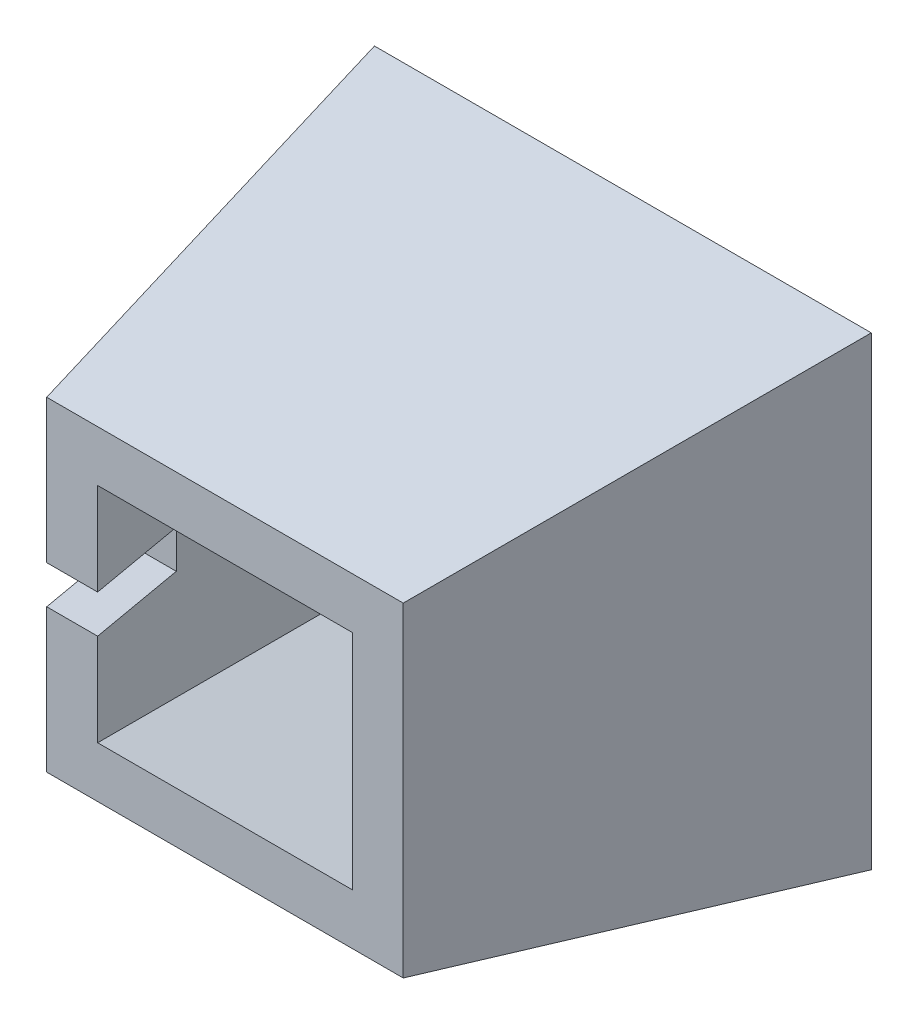
SolidWorks part; units mm, degrees
ref_plane "Front Plane" through (0, 0, 0) normal (0, 0, 1) x (1, 0, 0)
ref_plane "Top Plane" through (0, 0, 0) normal (0, 1, 0) x (1, 0, 0)
ref_plane "Right Plane" through (0, 0, 0) normal (1, 0, 0) x (0, 0, -1)
sketch "Sketch2" plane through (0, 0, 0) normal (0, 0, 1) x (1, 0, 0)
  line L1 (-56, -51) -> (56, -51)
  line L2 (-56, -51) -> (-56, 51)
  line L3 (-56, 51) -> (56, 51)
  line L4 (56, -51) -> (56, 51)
  line L5 (-56, -51) -> (56, 51) construction
  line L6 (-56, 51) -> (56, -51) construction
  point P0 (0, 0)
  dimension "D1" = 112
  dimension "D2" = 102
extrude "Boss-Extrude1" add sketch "Sketch2" against normal blind 125 draft 10 draft outward yes
sketch "Sketch3" plane through (0, 0, 0) normal (0, 0, -1) x (-1, 0, 0)
  line L1 (-40, -35) -> (40, -35)
  line L2 (-40, -35) -> (-40, 35)
  line L3 (-40, 35) -> (40, 35)
  line L4 (40, -35) -> (40, 35)
  line L5 (-40, -35) -> (40, 35) construction
  line L6 (-40, 35) -> (40, -35) construction
  point P0 (0, 0)
  dimension "D1" = 80
  dimension "D2" = 70
extrude "Cut-Extrude1" cut sketch "Sketch3" along normal up to next (125 mm away) draft 10 draft outward yes
ref_plane "Plane1" through (-60, 0, 0) normal (1, 0, 0) x (0, 0, -1)
sketch "Sketch5" plane through (-60, 0, 0) normal (1, 0, 0) x (0, 0, -1)
  line L0 (0, 51) -> (0, -51) construction
  line L1 (0, -6) -> (30, -6)
  line L2 (0, -6) -> (0, 6)
  line L3 (0, 6) -> (30, 6)
  line L4 (30, -6) -> (30, 6)
  dimension "D1" = 12
  dimension "D2" = 45
  dimension "D3" = 30
extrude "Cut-Extrude2" cut sketch "Sketch5" along normal up to next and the other way blind 10
